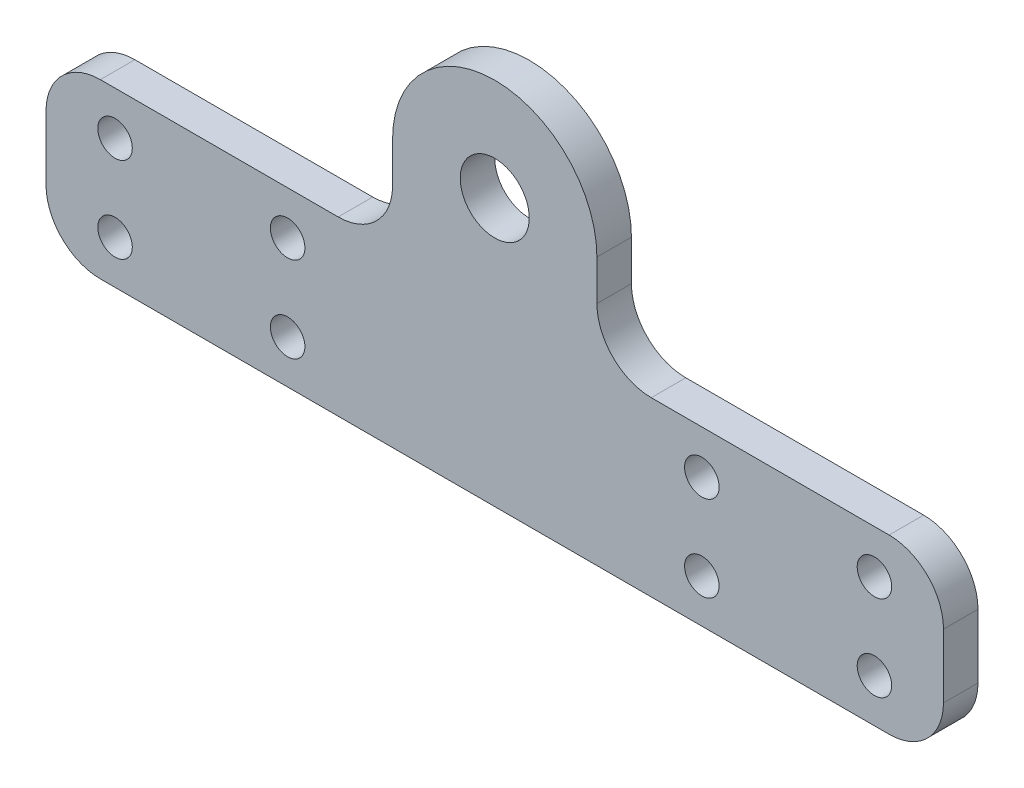
SolidWorks part; units mm, degrees
ref_plane "Front" through (0, 0, 0) normal (0, 0, 1) x (1, 0, 0)
ref_plane "Top" through (0, 0, 0) normal (0, 1, 0) x (1, 0, 0)
ref_plane "Right" through (0, 0, 0) normal (1, 0, 0) x (0, 0, -1)
ref_axis "side-side" through (80.9, 0, 0) along (-1, 0, 0)
ref_axis "up-down" through (0, 50, 0) along (0, -1, 0)
ref_axis "front-back" through (0, 0, -80.9) along (0, 0, 1)
sketch "Sketch1" plane through (0, 0, 0) normal (0, 0, 1) x (1, 0, 0)
  line L0 (-41.275, 132.779) -> (41.275, 132.779) construction
  line L1 (-41.275, -8.7) -> (-14.398, -8.7)
  line L2 (-41.275, -8.7) -> (-41.275, -24.575)
  line L3 (-41.275, -24.575) -> (41.275, -24.575)
  line L4 (41.275, -8.7) -> (41.275, -24.575)
  line L6 (-9.398, -3.7) -> (-9.398, 0)
  line L7 (-9.398, 0) -> (9.398, 0) construction
  line L8 (9.398, -3.7) -> (9.398, 0)
  line L9 (-41.275, 132.779) -> (-41.275, 116.904) construction
  line L10 (14.398, -8.7) -> (41.275, -8.7)
  line L11 (0, 0) -> (0, -39.6614) construction
  circle A0 centre (0, 0) radius 3.175
  arc A1 (-9.398, 0) -> (9.398, 0) centre (0, 0) cw
  circle A2 centre (0, 88.9) radius 3.175 construction
  arc A3 (-9.398, 88.9) -> (9.398, 88.9) centre (0, 88.9) ccw construction
  circle A4 centre (-34.925, -12.7) radius 1.5875
  circle A5 centre (-34.925, -20.575) radius 1.5875
  circle A6 centre (-19.05, -12.7) radius 1.5875
  circle A7 centre (-19.05, -20.575) radius 1.5875
  circle A8 centre (-34.925, 120.904) radius 1.5875 construction
  arc A9 (14.398, -8.7) -> (9.398, -3.7) centre (14.398, -3.7) cw
  arc A10 (-14.398, -8.7) -> (-9.398, -3.7) centre (-14.398, -3.7) ccw
  circle A11 centre (19.05, -20.575) radius 1.5875
  circle A12 centre (19.05, -12.7) radius 1.5875
  circle A13 centre (34.925, -20.575) radius 1.5875
  circle A14 centre (34.925, -12.7) radius 1.5875
  dimension "D3" = 12.7
  dimension "D4" = 5
  dimension "D1" = 4
  dimension "D2" = 4
extrude "Boss-Extrude1" add sketch "Sketch1" along normal blind 3.175
fillet "Fillet1" radius 5 4 edges at (41.275, -24.575, 1.5875) (41.275, -8.7, 1.5875) (-41.275, -24.575, 1.5875) (-41.275, -8.7, 1.5875)
